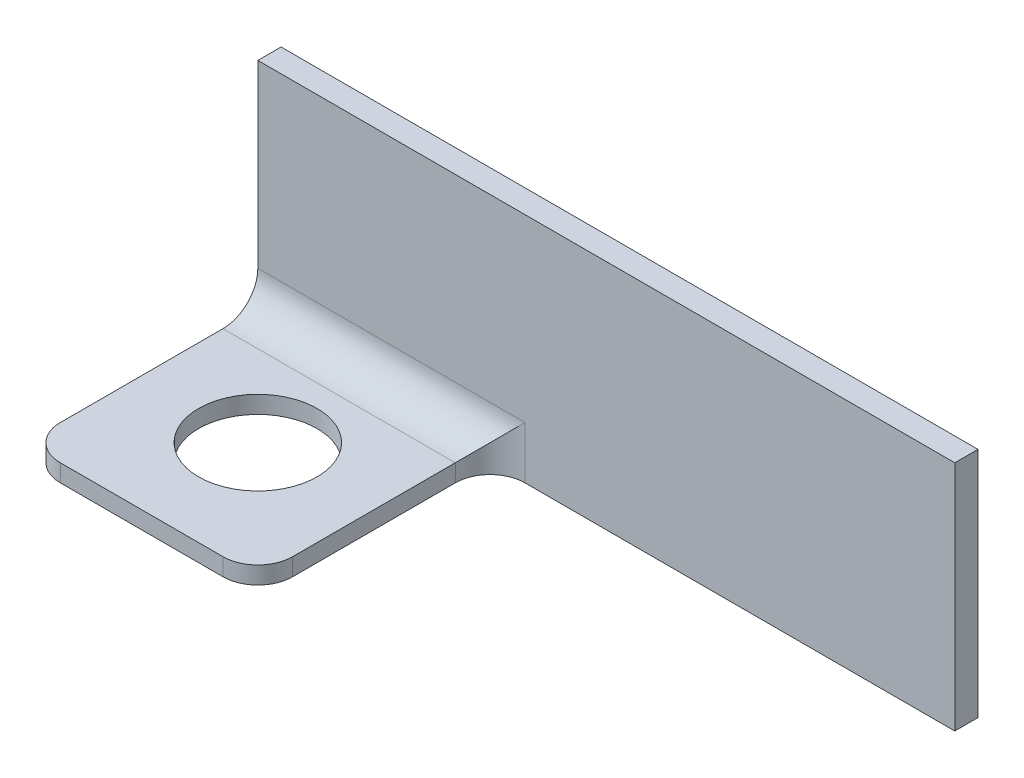
SolidWorks part; units mm, degrees
ref_plane "Front Plane" through (0, 0, 0) normal (0, 0, 1) x (1, 0, 0)
ref_plane "Top Plane" through (0, 0, 0) normal (0, 1, 0) x (1, 0, 0)
ref_plane "Right Plane" through (0, 0, 0) normal (1, 0, 0) x (0, 0, -1)
sketch "Sketch1" plane through (0, 0, 0) normal (0, 1, 0) x (1, 0, 0)
  line L1 (10, 10) -> (-10, 10)
  line L2 (10, 10) -> (10, -10)
  line L3 (10, -10) -> (-10, -10)
  line L4 (-10, 10) -> (-10, -10)
  line L5 (10, 10) -> (-10, -10) construction
  line L6 (10, -10) -> (-10, 10) construction
  line L7 (-10, 10) -> (50, 10)
  line L8 (-10, 10) -> (-10, 12)
  line L9 (-10, 12) -> (50, 12)
  line L10 (50, 10) -> (50, 12)
  circle A0 centre (0, 0) radius 5.1
  dimension "D1" = 10.2
  dimension "D2" = 20
  dimension "D3" = 20
  dimension "D4" = 60
  dimension "D5" = 2
extrude "Boss-Extrude2" add sketch "Sketch1" along normal blind 1.5 contours L1 L4 L3 L2 A0 region at (9.7172, 0, 0)
extrude "Boss-Extrude3" add sketch "Sketch1<4>" along normal blind 20 contours L8 L9 L10 L7
sketch "Sketch1<4>" plane through (0, 0, 0) normal (0, 1, 0) x (1, 0, 0) same geometry as "Sketch1"
fillet "Fillet1" radius 3 1 edges at (0, 1.5, -10)
fillet "Fillet2" radius 3 1 edges at (10, 2.25, -10)
fillet "Fillet3" radius 3 2 edges at (10, 0.75, 10) (-10, 0.75, 10)
